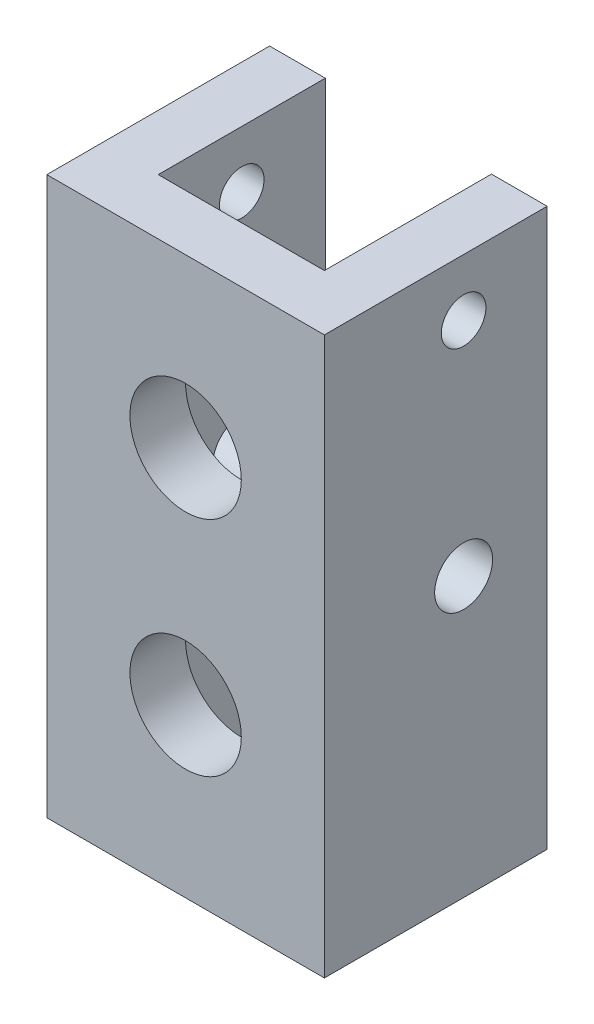
SolidWorks part; units mm, degrees
ref_plane "Front Plane" through (0, 0, 0) normal (0, 0, 1) x (1, 0, 0)
ref_plane "Top Plane" through (0, 0, 0) normal (0, 1, 0) x (1, 0, 0)
ref_plane "Right Plane" through (0, 0, 0) normal (1, 0, 0) x (0, 0, -1)
sketch "Sketch1" plane through (0, 0, 0) normal (0, 1, 0) x (1, 0, 0)
  line L0 (0, 0) -> (0, 25.4)
  line L1 (0, 25.4) -> (6.35, 25.4)
  line L2 (6.35, 25.4) -> (6.35, 6.35)
  line L3 (6.35, 6.35) -> (25.2944, 6.35)
  line L7 (31.6444, 0) -> (0, 0)
  line L8 (15.8222, 0) -> (15.8222, 6.35) construction
  line L9 (31.6444, 25.4) -> (25.2944, 25.4)
  line L10 (25.2944, 25.4) -> (25.2944, 6.35)
  line L11 (31.6444, 0) -> (31.6444, 25.4)
  dimension "D1" = 6.35
  dimension "D2" = 6.35
  dimension "D3" = 25.4
extrude "Boss-Extrude1" add sketch "Sketch1" along normal blind 63.5
sketch "Sketch2" plane through (0, 0, 0) normal (0, 0, 1) x (1, 0, 0)
  line L0 (15.8222, 63.5) -> (15.8222, 0) construction
  line L1 (0, 63.5) -> (31.6444, 63.5) construction
  line L2 (0, 0) -> (31.6444, 0) construction
  circle A0 centre (15.8222, 44.45) radius 6.35
  circle A1 centre (15.8222, 19.05) radius 6.35
  point P8 (15.8222, 31.75)
  dimension "D1" = 25.4
  dimension "D2" = 12.7
extrude "Cut-Extrude1" cut sketch "Sketch2" against normal through all
sketch "Sketch5" plane through (6.35, 0, 0) normal (1, 0, 0) x (0, 0, -1)
  line L0 (6.35, 31.75) -> (25.4, 31.75) construction
  line L1 (6.35, 63.5) -> (6.35, 0) construction
  line L2 (25.4, 63.5) -> (25.4, 0) construction
  line L3 (15.875, 63.5) -> (15.875, 0) construction
  line L4 (6.35, 63.5) -> (25.4, 63.5) construction
  line L5 (6.35, 0) -> (25.4, 0) construction
  circle A0 centre (15.875, 31.75) radius 3.302
  circle A1 centre (15.875, 56.99) radius 2.54
extrude "Cut-Extrude2" cut sketch "Sketch5" against normal through all and the other way through all
